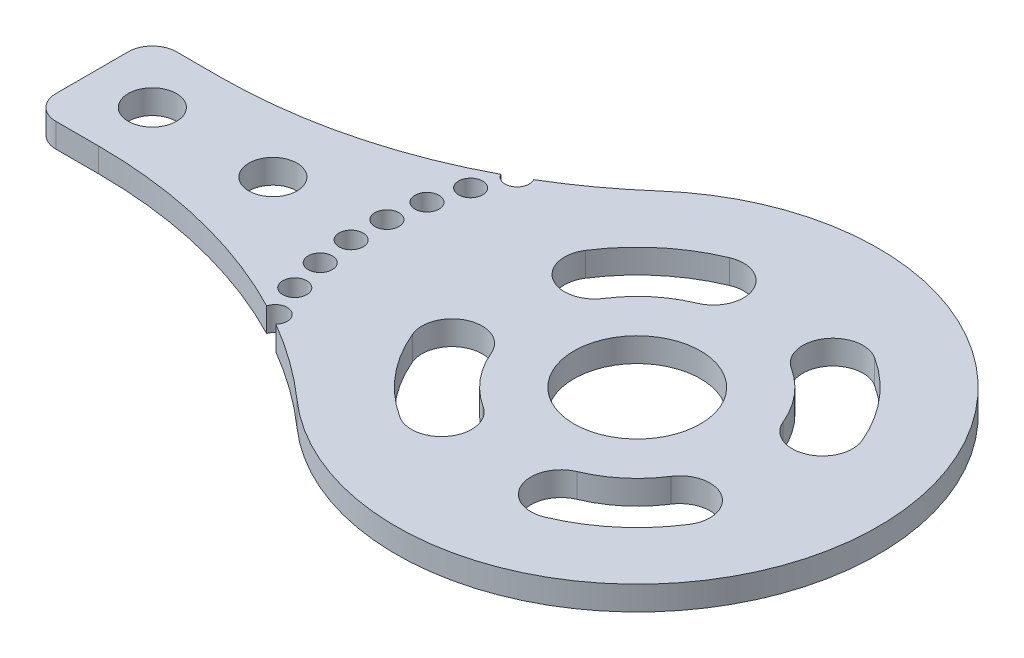
SolidWorks part; units mm, degrees
ref_plane "Спереди" through (0, 0, 0) normal (0, 0, 1) x (1, 0, 0)
ref_plane "Сверху" through (0, 0, 0) normal (0, 1, 0) x (1, 0, 0)
ref_plane "Справа" through (0, 0, 0) normal (1, 0, 0) x (0, 0, -1)
sketch "Эскиз1" plane through (0, 0, 0) normal (0, 1, 0) x (1, 0, 0)
  line L0 (0, -2) -> (0, -8)
  line L1 (2, -10) -> (5.5425, -10)
  line L2 (2, 0) -> (5.5425, 0)
  line L3 (5.5425, 0) -> (5.5425, -10) construction
  arc A0 (32, -20) -> (32, 10) centre (45.2288, -5) ccw
  arc A1 (5.5425, -10) -> (32, -20) centre (5.5425, -50) cw
  arc A2 (5.5425, 0) -> (32, 10) centre (5.5425, 40) ccw
  arc A3 (0, -8) -> (2, -10) centre (2, -8) ccw
  arc A4 (0, -2) -> (2, 0) centre (2, -2) cw
  point P12 (0, -10)
  point P15 (0, 0)
  dimension "D2" = 40
  dimension "D3" = 2
  dimension "D4" = 20
  dimension "D1" = 10
  dimension "D5" = 32
extrude "Бобышка-Вытянуть1" add sketch "Эскиз1" along normal blind 2
sketch "Эскиз2" plane through (0, 2, 0) normal (0, 1, 0) x (1, 0, 0)
  circle A2 centre (25.1372, 5.1281) radius 1
  circle A4 centre (45.2288, -5) radius 22.5 construction
  arc A5 (32, -20) -> (32, 10) centre (45.2288, -5) ccw construction
  arc A6 (5.5425, 0) -> (32, 10) centre (5.5425, 40) ccw construction
  dimension "D1" = 2
  dimension "D2" = 45
extrude "Вырез-Вытянуть1" cut sketch "Эскиз2" against normal through all
pattern_circular "Круговой массив1" count 8 every 7.5 about axis through (45.2288, 2, 5) along (0, 1, 0) of "Вырез-Вытянуть1"
sketch "Эскиз3" plane through (0, 2, 0) normal (0, 1, 0) x (1, 0, 0)
  line L0 (0, -2) -> (0, -8) construction
  line L3 (5, -10) -> (5, 0) construction
  line L4 (2, -10) -> (5.5425, -10) construction
  line L5 (5.5425, 0) -> (2, 0) construction
  circle A0 centre (5, -5) radius 2
  dimension "D1" = 4
  dimension "D2" = 5
extrude "Вырез-Вытянуть2" cut sketch "Эскиз3" against normal through all
pattern_linear "Линейный массив1" count 2 spacing 10 along (1, 0, 0) of "Вырез-Вытянуть2"
sketch "Эскиз4" plane through (0, 2, 0) normal (0, 1, 0) x (1, 0, 0)
  circle A0 centre (45.2288, -5) radius 11.75 construction
  arc A1 (32, -20) -> (32, 10) centre (45.2288, -5) ccw construction
  circle A2 centre (45.2288, 6.75) radius 2
  dimension "D1" = 4
  dimension "D2" = 23.5
extrude "Вырез-Вытянуть3" [suppressed] cut sketch "Эскиз4" against normal through all
pattern_circular "Круговой массив2" [suppressed] count 8 every 45 of bodies 108
sketch "Эскиз6" plane through (0, 2, 0) normal (0, 1, 0) x (1, 0, 0)
  line L0 (45.2288, -5) -> (34.7269, 5.5019) construction
  line L1 (45.2288, -5) -> (35.4788, -5) construction
  arc A0 (41.6704, 3.5381) -> (37.4462, -0.0008) centre (45.2288, -5) ccw
  arc A1 (32, -20) -> (32, 10) centre (45.2288, -5) ccw construction
  arc A2 (39.747, 8.1533) -> (33.2394, 2.7016) centre (45.2288, -5) ccw
  circle A4 centre (35.3428, 1.3504) radius 2.5
  circle A5 centre (40.7087, 5.8457) radius 2.5
  circle M8 centre (15, -5) radius 2
  dimension "D1" = 5
  dimension "D2" = 5
  dimension "D3" = 45
  dimension "D4" = 11.7499
  dimension "D5" = 7
extrude "Вырез-Вытянуть4" cut sketch "Эскиз6" against normal through all contours A4 | A5 A2 A4 A0 | A5 M8 region at (37.5163, 2, -4.2062) region at (40.7087, 2, -5.8457) region at (35.3428, 2, -1.3504)
pattern_circular "Круговой массив3" count 4 over 360 about axis through (45.2288, 2, 5) along (0, 1, 0) of "Вырез-Вытянуть4"
sketch "Эскиз7" plane through (0, 2, 0) normal (0, 1, 0) x (1, 0, 0)
  circle A0 centre (45.2288, -5) radius 5.25
  arc A1 (32, -20) -> (32, 10) centre (45.2288, -5) ccw construction
  dimension "D1" = 10.5
extrude "Вырез-Вытянуть5" cut sketch "Эскиз7" against normal through all
equation "\"thick\"= \"thick@балка.SLDASM\""
equation "\"D1@Бобышка-Вытянуть1\"=\"thick\""
